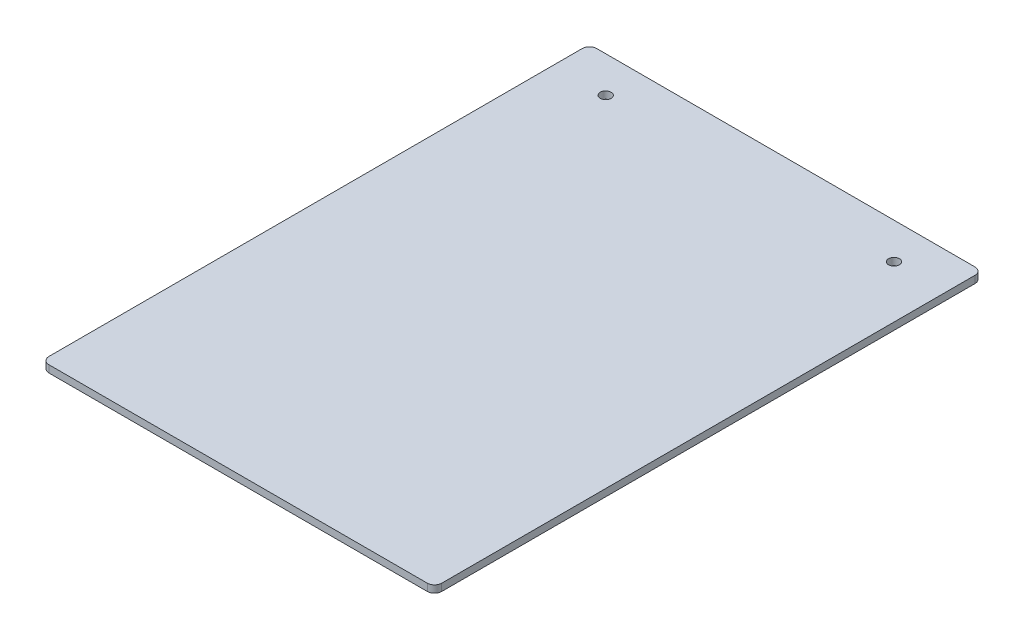
SolidWorks part; units mm, degrees
material "PC High Viscosity"
ref_plane "Front Plane" through (0, 0, 0) normal (0, 0, 1) x (1, 0, 0)
ref_plane "Top Plane" through (0, 0, 0) normal (0, 1, 0) x (1, 0, 0)
ref_plane "Right Plane" through (0, 0, 0) normal (1, 0, 0) x (0, 0, -1)
sketch "Sketch1" plane through (0, 0, 0) normal (0, 1, 0) x (1, 0, 0)
  line L1 (-173.0375, -241.3) -> (173.0375, -241.3)
  line L2 (-173.0375, -241.3) -> (-173.0375, 241.3)
  line L3 (-173.0375, 241.3) -> (173.0375, 241.3)
  line L4 (173.0375, -241.3) -> (173.0375, 241.3)
  line L5 (-173.0375, -241.3) -> (173.0375, 241.3) construction
  line L6 (-173.0375, 241.3) -> (173.0375, -241.3) construction
  point P0 (0, 0)
  dimension "D1" = 482.6
  dimension "D2" = 346.075
extrude "Boss-Extrude1" add sketch "Sketch1" along normal blind 6.35
fillet "Fillet1" radius 6.35 4 edges at (173.0375, 3.175, -241.3) (-173.0375, 3.175, -241.3) (-173.0375, 3.175, 241.3) (173.0375, 3.175, 241.3)
hole_wizard "3/8 (0.375) Diameter Hole1" positions "Sketch2" profile "Sketch3" hole size "3/8" standard "ANSI Inch" end condition through all
sketch "Sketch2" plane through (0, 6.35, 0) normal (0, 1, 0) x (1, 0, 0)
  line L0 (0, 241.3) -> (0, -241.3) construction
  line L1 (166.6875, 241.3) -> (-166.6875, 241.3) construction
  line L2 (-166.6875, -241.3) -> (166.6875, -241.3) construction
  point P0 (-127, 209.55)
  point P2 (127, 209.55)
  point P12 (0, 0)
  dimension "D1" = 31.75
  dimension "D2" = 127
sketch "Sketch3" plane through (-127, 6.35, -209.55) normal (1, 0, 0) x (0, 0, 1)
  line L0 (0, 0) -> (0, 6.35)
  line L1 (0, 6.35) -> (4.7625, 6.35)
  line L2 (4.7625, 6.35) -> (4.7625, 0)
  line L5 (4.7625, 0) -> (0, 0)
  line L11 (0, -6.35) -> (0, 107.95) construction
  dimension "Thru Hole Dia." = 9.525
  dimension "Thru Hole Depth" = 6.35
